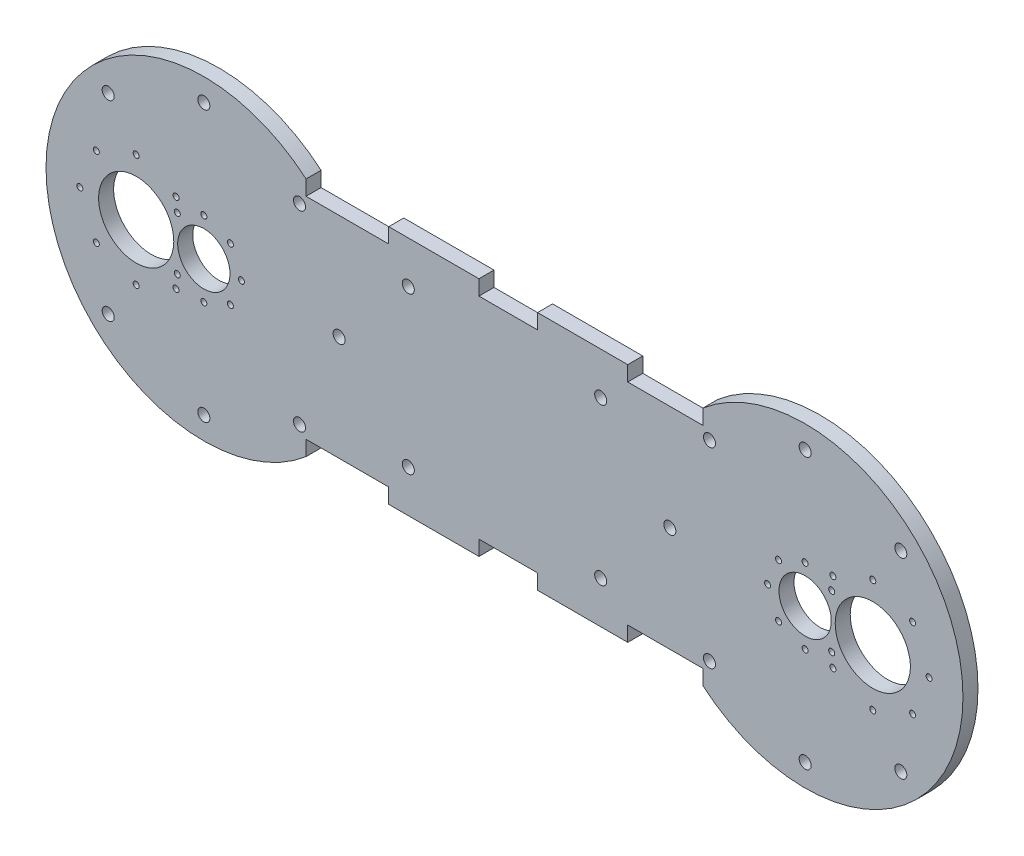
SolidWorks part; units mm, degrees
material "ABS"
ref_plane "Front Plane" through (0, 0, 0) normal (0, 0, 1) x (1, 0, 0)
ref_plane "Top Plane" through (0, 0, 0) normal (0, 1, 0) x (1, 0, 0)
ref_plane "Right Plane" through (0, 0, 0) normal (1, 0, 0) x (0, 0, -1)
sketch "Sketch1" plane through (0, 0, 0) normal (0, 0, 1) x (1, 0, 0)
  line L0 (-87.4716, -41.275) -> (87.4716, -41.275) construction
  line L1 (-83.8153, 50.8) -> (83.8153, 50.8)
  line L2 (-87.4716, 41.275) -> (87.4716, 41.275) construction
  line L3 (-83.8153, -50.8) -> (83.8153, -50.8)
  line L4 (0, 0) -> (0, 100.7987) construction
  arc A0 (-87.4716, 41.275) -> (-87.4716, -41.275) centre (-127, 0) ccw construction
  arc A1 (87.4716, -41.275) -> (87.4716, 41.275) centre (127, 0) ccw construction
  circle A2 centre (-127, 0) radius 3.175
  circle A3 centre (127, 0) radius 3.175
  arc A4 (-83.8153, 50.8) -> (-83.8153, -50.8) centre (-127, 0) ccw
  arc A5 (83.8153, -50.8) -> (83.8153, 50.8) centre (127, 0) ccw
  circle A6 centre (-127, 57.15) radius 2.54
  circle A7 centre (-86.5888, 40.4112) radius 2.54
  circle A8 centre (-69.85, 0) radius 2.54
  circle A9 centre (-86.5888, -40.4112) radius 2.54
  circle A10 centre (-127, -57.15) radius 2.54
  circle A11 centre (-167.4112, -40.4112) radius 2.54
  circle A12 centre (-184.15, 0) radius 2.54 [skipped]
  circle A13 centre (-167.4112, 40.4112) radius 2.54
  circle A14 centre (127, 57.15) radius 2.54
  circle A15 centre (167.4112, 40.4112) radius 2.54
  circle A16 centre (167.4112, -40.4112) radius 2.54
  circle A17 centre (127, -57.15) radius 2.54
  circle A18 centre (86.5888, -40.4112) radius 2.54
  circle A19 centre (69.85, 0) radius 2.54
  circle A20 centre (86.5888, 40.4112) radius 2.54
  point P0 (0, 0)
  dimension "D3" = 6.35
  dimension "D4" = 6.35
  dimension "D6" = 133.35
  dimension "D7" = 133.35
  dimension "D2" = 5.08
  dimension "D5" = 8
  dimension "D1" = 9.525
extrude "Boss-Extrude1" add sketch "Sketch1" along normal mid plane 6.35
sketch "Sketch2" plane through (0, 0, 3.175) normal (0, 0, 1) x (1, 0, 0)
  line L0 (-127, 0) -> (-207.737, 0) construction
  line L4 (0, 0) -> (0, 93.9723) construction
  circle A0 centre (-127, 0) radius 11.049
  circle A1 centre (-155.575, 0) radius 15.875
  circle A2 centre (127, 0) radius 15.875 construction
  circle A3 centre (155.575, 0) radius 23.8125 construction
  circle A4 centre (-155.575, 0) radius 23.8125 construction
  circle A5 centre (-127, 0) radius 15.875 construction
  circle A6 centre (-155.575, 23.8125) radius 1.27
  circle A7 centre (-138.737, 16.838) radius 1.27
  circle A8 centre (-131.7625, 0) radius 1.27 [skipped]
  circle A9 centre (-138.737, -16.838) radius 1.27
  circle A10 centre (-155.575, -23.8125) radius 1.27
  circle A11 centre (-172.413, -16.838) radius 1.27
  circle A12 centre (-179.3875, 0) radius 1.27
  circle A13 centre (-172.413, 16.838) radius 1.27
  circle A14 centre (-127, 15.875) radius 1.27
  circle A15 centre (-115.7747, 11.2253) radius 1.27
  circle A16 centre (-111.125, 0) radius 1.27
  circle A17 centre (-115.7747, -11.2253) radius 1.27
  circle A18 centre (-127, -15.875) radius 1.27
  circle A19 centre (-138.2253, -11.2253) radius 1.27
  circle A20 centre (138.2253, 11.2253) radius 1.27
  circle A21 centre (-138.2253, 11.2253) radius 1.27
  circle A22 centre (-142.875, 0) radius 1.27 [skipped]
  circle A23 centre (138.2253, -11.2253) radius 1.27
  circle A24 centre (127, -15.875) radius 1.27
  circle A25 centre (115.7747, -11.2253) radius 1.27
  circle A26 centre (111.125, 0) radius 1.27
  circle A27 centre (115.7747, 11.2253) radius 1.27
  circle A28 centre (127, 15.875) radius 1.27
  circle A29 centre (172.413, 16.838) radius 1.27
  circle A30 centre (179.3875, 0) radius 1.27
  circle A31 centre (172.413, -16.838) radius 1.27
  circle A32 centre (155.575, -23.8125) radius 1.27
  circle A33 centre (138.737, -16.838) radius 1.27
  circle A34 centre (138.737, 16.838) radius 1.27
  circle A35 centre (155.575, 23.8125) radius 1.27
  circle A36 centre (155.575, 0) radius 15.875
  circle A37 centre (127, 0) radius 11.049
  dimension "D2" = 28.575
  dimension "D3" = 31.75
  dimension "D4" = 31.75
  dimension "D5" = 47.625
  dimension "D6" = 2.54
  dimension "D1" = 22.098
  dimension "D8" = 2.54
  dimension "D7" = 8
  dimension "D9" = 8
extrude "Cut-Extrude1" cut sketch "Sketch2" against normal through all
sketch "Sketch3" plane through (0, 0, 3.175) normal (0, 0, 1) x (1, 0, 0)
  line L1 (-40.64, 33.02) -> (40.64, 33.02) construction
  line L2 (-40.64, 33.02) -> (-40.64, -33.02) construction
  line L3 (-40.64, -33.02) -> (40.64, -33.02) construction
  line L4 (40.64, 33.02) -> (40.64, -33.02) construction
  line L5 (-40.64, 33.02) -> (40.64, -33.02) construction
  line L6 (-40.64, -33.02) -> (40.64, 33.02) construction
  circle A0 centre (-40.64, 33.02) radius 2.54
  circle A1 centre (40.64, 33.02) radius 2.54
  circle A2 centre (40.64, -33.02) radius 2.54
  circle A3 centre (-40.64, -33.02) radius 2.54
  point P0 (0, 0)
  dimension "D3" = 5.08
  dimension "D4" = 5.08
  dimension "D5" = 5.08
  dimension "D6" = 5.08
  dimension "D1" = 81.28
  dimension "D2" = 66.04
extrude "Cut-Extrude2" cut sketch "Sketch3" against normal through all
sketch "Sketch4" plane through (0, 0, 3.175) normal (0, 0, 1) x (1, 0, 0)
  line L0 (83.8153, 50.8) -> (-83.8153, 50.8) construction
  line L1 (-83.8153, 50.8) -> (-48.8903, 50.8)
  line L2 (-83.8153, 50.8) -> (-83.8153, 44.45)
  line L3 (-83.8153, 44.45) -> (-48.8903, 44.45)
  line L4 (-48.8903, 50.8) -> (-48.8903, 44.45)
  line L5 (-10.7903, 50.8) -> (13.9653, 50.8)
  line L6 (-10.7903, 50.8) -> (-10.7903, 44.45)
  line L7 (-10.7903, 44.45) -> (13.9653, 44.45)
  line L8 (13.9653, 50.8) -> (13.9653, 44.45)
  line L9 (-44.294, 0) -> (227.942, 0) construction
  line L10 (83.8153, 50.8) -> (52.0653, 50.8)
  line L11 (83.8153, 50.8) -> (83.8153, 44.45)
  line L12 (83.8153, 44.45) -> (52.0653, 44.45)
  line L13 (52.0653, 50.8) -> (52.0653, 44.45)
  line L14 (52.0653, -50.8) -> (52.0653, -44.45)
  line L15 (83.8153, -44.45) -> (52.0653, -44.45)
  line L16 (83.8153, -50.8) -> (83.8153, -44.45)
  line L17 (83.8153, -50.8) -> (52.0653, -50.8)
  line L18 (13.9653, -50.8) -> (13.9653, -44.45)
  line L19 (-10.7903, -44.45) -> (13.9653, -44.45)
  line L20 (-10.7903, -50.8) -> (-10.7903, -44.45)
  line L21 (-10.7903, -50.8) -> (13.9653, -50.8)
  line L22 (-48.8903, -50.8) -> (-48.8903, -44.45)
  line L23 (-83.8153, -44.45) -> (-48.8903, -44.45)
  line L24 (-83.8153, -50.8) -> (-83.8153, -44.45)
  line L25 (-83.8153, -50.8) -> (-48.8903, -50.8)
  dimension "D1" = 6.35
  dimension "D2" = 34.925
  dimension "D3" = 38.1
  dimension "D4" = 31.75
  dimension "D5" = 38.1
extrude "Cut-Extrude3" cut sketch "Sketch4" against normal through all
